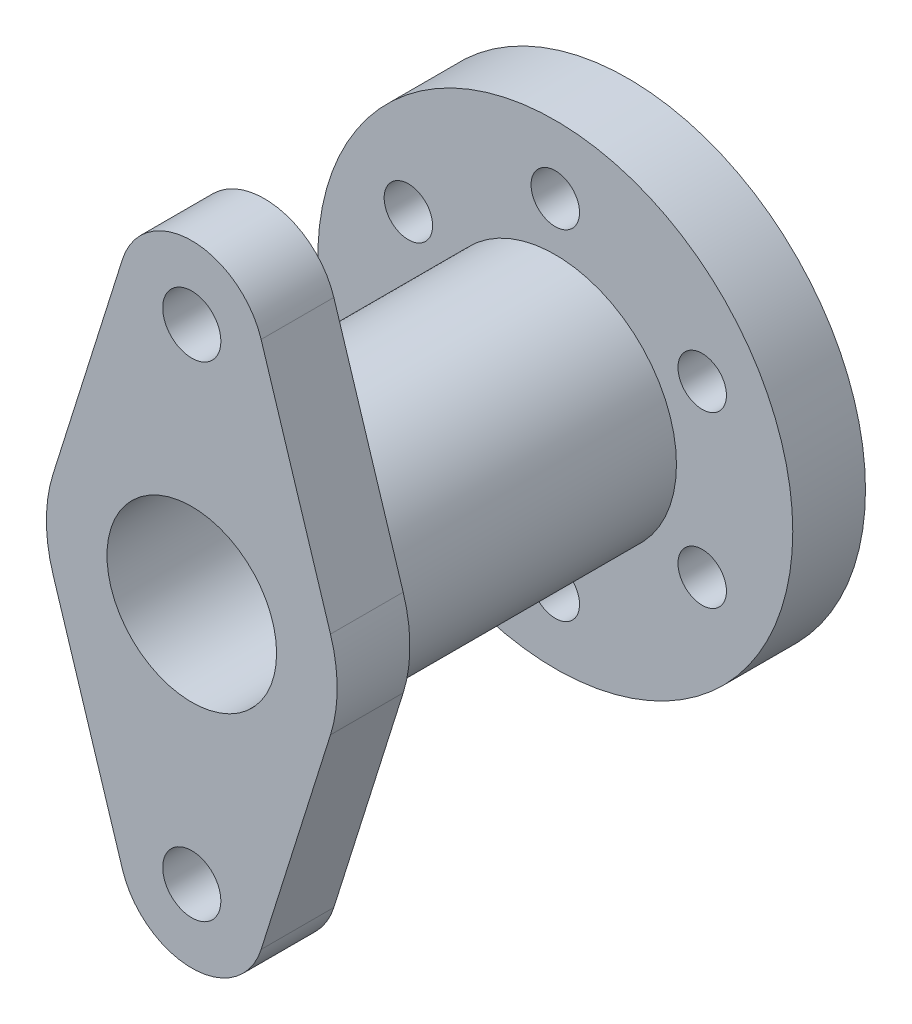
SolidWorks part; units mm, degrees
ref_plane "Front Plane" through (0, 0, 0) normal (0, 0, 1) x (1, 0, 0)
ref_plane "Top Plane" through (0, 0, 0) normal (0, 1, 0) x (1, 0, 0)
ref_plane "Right Plane" through (0, 0, 0) normal (1, 0, 0) x (0, 0, -1)
sketch "Sketch1" plane through (0, 0, 0) normal (0, 0, 1) x (1, 0, 0)
  circle A0 centre (0, 0) radius 49
  dimension "D1" = 98
extrude "Boss-Extrude1" add sketch "Sketch1" along normal blind 15
sketch "Sketch7" plane through (0, 0, 15) normal (0, 0, 1) x (1, 0, 0)
  circle A0 centre (0, 0) radius 35 construction
  circle A1 centre (0, 35) radius 5
  circle A2 centre (30.3109, 17.5) radius 5
  circle A3 centre (30.3109, -17.5) radius 5
  circle A4 centre (0, -35) radius 5
  circle A5 centre (-30.3109, -17.5) radius 5
  circle A6 centre (-30.3109, 17.5) radius 5
  circle A7 centre (0, 0) radius 49 construction
  point P18 (0, 0)
  dimension "D1" = 70
  dimension "D2" = 10
  dimension "D3" = 6
extrude "Cut-Extrude1" cut sketch "Sketch7" against normal through all
sketch "Sketch8" plane through (0, 0, 15) normal (0, 0, 1) x (1, 0, 0)
  circle A0 centre (0, 0) radius 25
  dimension "D1" = 50
extrude "Boss-Extrude2" add sketch "Sketch8" along normal blind 60
sketch "Sketch10" plane through (0, 0, 75) normal (0, 0, 1) x (1, 0, 0)
  line L0 (0, 77.7512) -> (0, -85.6157) construction
  line L1 (-85.6157, 0) -> (93.8377, 0) construction
  line L2 (29.1794, -7.2153) -> (14.3091, -54.5)
  line L3 (-28.6182, -9) -> (-14.3091, -54.5)
  line L4 (-14.3091, 54.5) -> (-28.6182, 9)
  line L5 (14.3091, 54.5) -> (28.6182, 9)
  circle A0 centre (0, 0) radius 30
  circle A1 centre (0, 50) radius 15
  circle A2 centre (0, -50) radius 15
  circle A3 centre (0, 0) radius 25 construction
  point P19 (0, 0)
  circle M8 centre (0, 0) radius 25
  dimension "D1" = 60
  dimension "D2" = 50
  dimension "D4" = 30
  dimension "D3" = 100
extrude "Boss-Extrude3" add sketch "Sketch10" along normal blind 15 contours A1 | A1 L4 A0 L5 | A2 | A2 L2 A0 L3 | M8 | A0 M8 region at (0, -32.6311, 75) region at (0, -29.1515, 75) region at (0, -50, 75) region at (0, 32.6311, 75) region at (0, 50, 75) region at (0, 0, 75)
sketch "Sketch11" plane through (0, 0, 90) normal (0, 0, 1) x (1, 0, 0)
  circle A0 centre (0, 50) radius 6
  circle A1 centre (0, -50) radius 6
  circle A2 centre (0, 0) radius 17.5
  dimension "D1" = 12
  dimension "D2" = 35
extrude "Cut-Extrude3" cut sketch "Sketch11" against normal blind 33 contours A0 | A1
extrude "Cut-Extrude4" cut sketch "Sketch11<3>" against normal blind 30
sketch "Sketch11<3>" plane through (0, 0, 90) normal (0, 0, 1) x (1, 0, 0) same geometry as "Sketch11"
sketch "Sketch12" plane through (0, 0, 0) normal (0, 0, -1) x (-1, 0, 0)
  circle A0 centre (0, 0) radius 13
  dimension "D1" = 26
extrude "Cut-Extrude5" cut sketch "Sketch12" against normal blind 60
